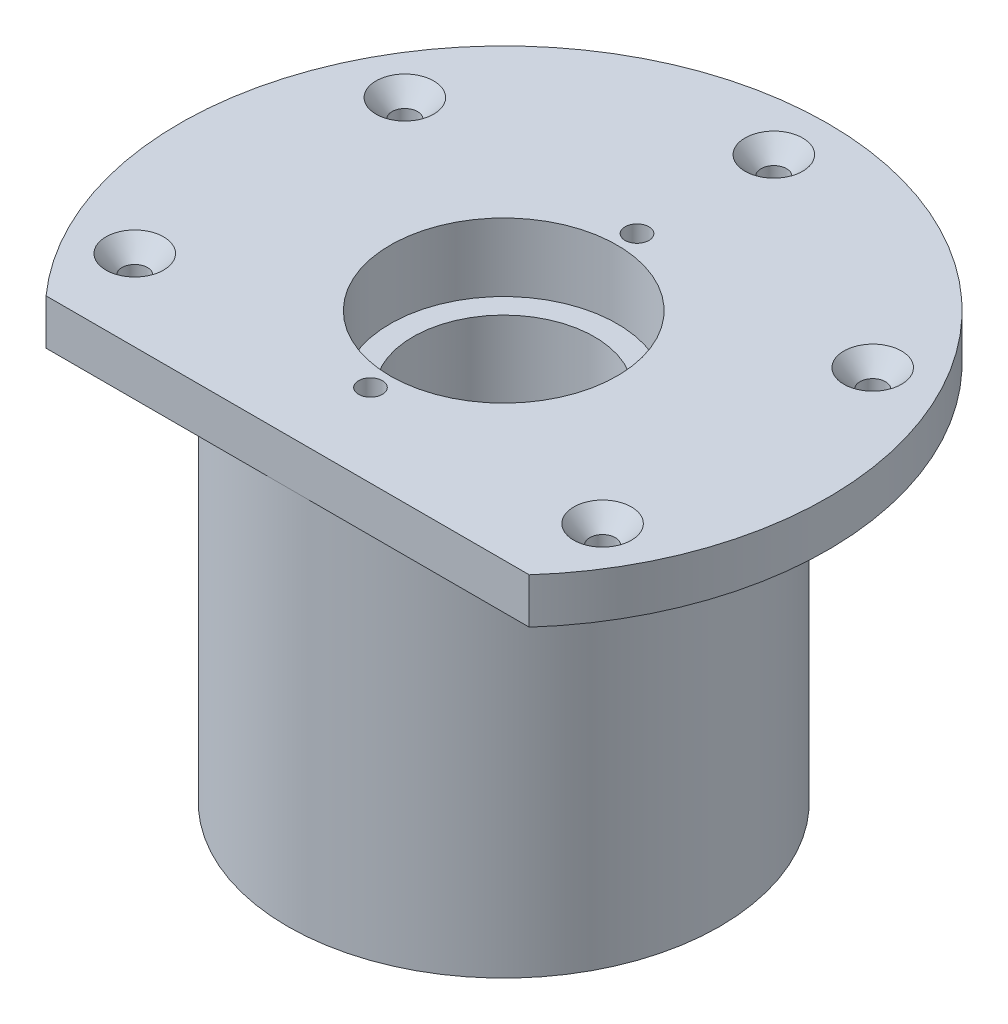
SolidWorks part; units mm, degrees
ref_plane "Front Plane" through (0, 0, 0) normal (0, 0, 1) x (1, 0, 0)
ref_plane "Top Plane" through (0, 0, 0) normal (0, 1, 0) x (1, 0, 0)
ref_plane "Right Plane" through (0, 0, 0) normal (1, 0, 0) x (0, 0, -1)
sketch "Sketch1" plane through (0, 0, 0) normal (0, 1, 0) x (1, 0, 0)
  circle A0 centre (0, 0) radius 38.1
  circle A1 centre (0, 0) radius 20
  dimension "D1" = 76.2
  dimension "D2" = 40
extrude "Boss-Extrude1" add sketch "Sketch1" along normal blind 75
sketch "Sketch2" plane through (0, 75, 0) normal (0, 1, 0) x (1, 0, 0)
  line L0 (-42.5971, -38.1) -> (42.5971, -38.1)
  circle A0 centre (0, 0) radius 57.15
  circle A1 centre (0, 0) radius 20 construction
  circle A2 centre (0, 0) radius 20
  circle A3 centre (0, 0) radius 38.1 construction
  circle M1 centre (0, 0) radius 38.1
  circle M2 centre (0, 0) radius 20
  dimension "D1" = 114.3
extrude "Boss-Extrude2" add sketch "Sketch2" against normal blind 8 contours L0 A0 M1 | M1 M2 region at (-26.1788, 75, -26.1788) region at (-19.8615, 75, -51.998)
hole_wizard "CSK for #8 Flat Head Machine Screw2" positions "Sketch3" profile "Sketch4" countersink size "#8" standard "ANSI Inch" end condition through all
sketch "Sketch3" plane through (0, 75, 0) normal (0, 1, 0) x (1, 0, 0)
  line L0 (-41.2445, -23.8125) -> (0, 0) construction
  line L2 (-41.25, 0) -> (41.25, 0) construction
  line L3 (-32.9956, -19.05) -> (-49.4934, -28.575) construction
  line L4 (0, 0) -> (-41.2445, -23.8125) construction
  arc A0 (42.5971, -38.1) -> (-42.5971, -38.1) centre (0, 0) ccw construction
  circle A1 centre (0, 0) radius 38.1 construction
  circle A2 centre (0, 0) radius 38.1 construction
  point P0 (-41.2445, -23.8125)
  point P32 (-41.2445, 23.8125)
  point P33 (0, 47.625)
  point P34 (41.2445, 23.8125)
  point P35 (41.2445, -23.8125)
  point P36 (0, -47.625) [skipped]
  dimension "D1" = 30
  dimension "D2" = 6
sketch "Sketch4" plane through (-41.2445, 75, 23.8125) normal (1, 0, 0) x (0, 0, 1)
  line L0 (0, 0) -> (0, 75)
  line L1 (0, 75) -> (2.2479, 75)
  line L2 (2.2479, 75) -> (2.2479, 3.2645)
  line L3 (2.2479, 3.2645) -> (5.0857, 0)
  line L5 (5.0857, 0) -> (0, 0)
  line L6 (-2.2479, 3.2645) -> (-5.0857, 0) construction
  line L11 (0, -6.35) -> (0, 107.95) construction
  dimension "Thru Hole Dia." = 4.4958
  dimension "Thru Hole Depth" = 75
  dimension "Near C'Sink Dia." = 10.1714
  dimension "Near C'Sink Angle" = 82
sketch "Sketch5" plane through (0, 75, 0) normal (0, 1, 0) x (1, 0, 0)
  circle A0 centre (0, 0) radius 20 construction
  circle A1 centre (0, 0) radius 20
  circle A2 centre (0, 0) radius 16
  dimension "D1" = 4
extrude "Boss-Extrude3" add sketch "Sketch5" against normal offset from surface (51 mm away) 12 from offset 12 up to face at (0, 0, 38.1) offset against normal yes
hole_wizard "Tap Drill for M5x0.8 Tap1" positions "Sketch6" profile "Sketch7" hole size "M5x0.8" standard "ANSI Metric" end condition through all
sketch "Sketch6" plane through (0, 75, 0) normal (0, 1, 0) x (1, 0, 0)
  point P0 (0, 23.5)
  point P2 (0, -23.5)
  dimension "D1" = 23.5
  dimension "D2" = 23.5
sketch "Sketch7" plane through (0, 75, -23.5) normal (1, 0, 0) x (0, 0, 1)
  line L0 (0, 0) -> (0, 75)
  line L1 (0, 75) -> (2.1, 75)
  line L2 (2.1, 75) -> (2.1, 0)
  line L5 (2.1, 0) -> (0, 0)
  line L11 (0, -6.35) -> (0, 107.95) construction
  dimension "Thru Hole Dia." = 4.2
  dimension "Thru Hole Depth" = 75
